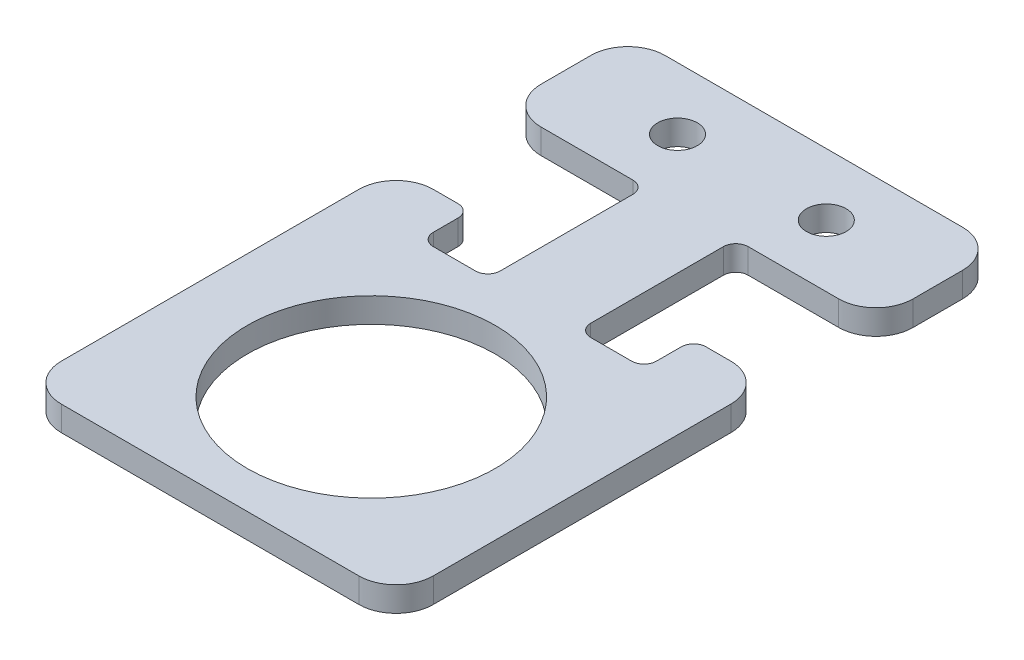
SolidWorks part; units mm, degrees
ref_plane "前视基准面" through (0, 0, 0) normal (0, 0, 1) x (1, 0, 0)
ref_plane "上视基准面" through (0, 0, 0) normal (0, 1, 0) x (1, 0, 0)
ref_plane "右视基准面" through (0, 0, 0) normal (1, 0, 0) x (0, 0, -1)
other "Configuration Table"
sketch "草图1" plane through (0, 0, 0) normal (0, 1, 0) x (1, 0, 0)
  line L0 (15, 15) -> (9, 15)
  line L1 (-15, -15) -> (15, -15)
  line L2 (-15, -15) -> (-15, 15)
  line L4 (15, -15) -> (15, 15)
  line L5 (-15, -15) -> (15, 15) construction
  line L6 (-15, 15) -> (15, -15) construction
  line L7 (-15, 15) -> (-9, 15)
  line L8 (-9, 15) -> (-9, 11)
  line L9 (-9, 11) -> (-3.6, 11)
  line L10 (-3.6, 11) -> (-3.6, 15)
  line L11 (9, 15) -> (9, 11)
  line L12 (9, 11) -> (3.7, 11)
  line L13 (3.7, 11) -> (3.7, 15)
  line L15 (-3.6, 15) -> (-3.6, 23.7)
  line L16 (3.7, 15) -> (3.7, 23.7)
  line L17 (3.7, 23.7) -> (15, 23.7)
  line L18 (-3.6, 23.7) -> (-15, 23.7)
  line L19 (15, 23.7) -> (15, 33.7)
  line L20 (15, 33.7) -> (-15, 33.7)
  line L21 (-15, 33.7) -> (-15, 23.7)
  point P0 (0, 0)
base flange "基体-法兰1" sketch "草图1" thickness 2 reverse thickness direction no parameters "D1"=10
sketch "草图6" plane through (0, 0, 0) normal (0, 1, 0) x (1, 0, 0)
  line L0 (-15, 28.7) -> (15, 28.7)
  line L1 (-15, 33.7) -> (-15, 23.7) construction
  line L2 (15, 23.7) -> (15, 33.7) construction
  line L3 (0, 28.7) -> (-6, 28.7)
  line L4 (0, 28.7) -> (6, 28.7)
  circle A0 centre (-6, 28.7) radius 1.6
  circle A1 centre (6, 28.7) radius 1.6
extrude "切除-拉伸1" cut sketch "草图6" against normal blind 10 contours L0 A0 | L0 A0 | L0 A1 L4 | L4 A1 L0 normal cut yes
fillet "圆角1" radius 3 8 edges at (-15, -1, -23.7) (-15, -1, -33.7) (15, -1, -33.7) (15, -1, -23.7) (15, -1, -15) (15, -1, 15) (-15, -1, 15) (-15, -1, -15)
fillet "圆角2" radius 1 8 edges at (-3.6, -1, -11) (-9, -1, -11) (-9, -1, -15) (-3.6, -1, -23.7) (3.7, -1, -23.7) (3.7, -1, -11) (9, -1, -11) (9, -1, -15)
sketch "草图7" plane through (0, 0, 0) normal (0, 1, 0) x (1, 0, 0)
  line L0 (-15, -2) -> (-12.6549, -2)
  line L5 (15, -2) -> (-15, -2)
  line L8 (-15, 12) -> (-15, -12) construction
  line L9 (15, -12) -> (15, 12) construction
  circle A1 centre (0, -2) radius 10
extrude "切除-拉伸3" cut sketch "草图7" against normal blind 10 contours L5 A1 | L5 A1 normal cut yes
sketch "折弯-线1" plane through (0, 0, 0) normal (0, 1, 0) x (1, 0, 0)
sketch "边界框1" plane through (0, 0, 0) normal (0, 1, 0) x (1, 0, 0)
sheet metal parameters "钣金6" thickness 2 parameters "D1"=10
flat pattern "平板型式6" [suppressed]
sketch "折弯-线2" plane through (0, 0, 0) normal (0, 1, 0) x (1, 0, 0)
sketch "边界框2" [suppressed] plane through (0, 0, 0) normal (0, 1, 0) x (1, 0, 0)
sheet metal parameters "钣金7" thickness 2 parameters "D1"=10
flat pattern "平板型式6"
sketch "折弯-线2" plane through (0, 0, 0) normal (0, 1, 0) x (1, 0, 0)
sketch "边界框2" [suppressed] plane through (0, 0, 0) normal (0, 1, 0) x (1, 0, 0)
sheet metal parameters "钣金9" thickness 2 parameters "D1"=10
flat pattern "平板型式6"
sketch "折弯-线2" plane through (0, 0, 0) normal (0, 1, 0) x (1, 0, 0)
sketch "边界框2" [suppressed] plane through (0, 0, 0) normal (0, 1, 0) x (1, 0, 0)
